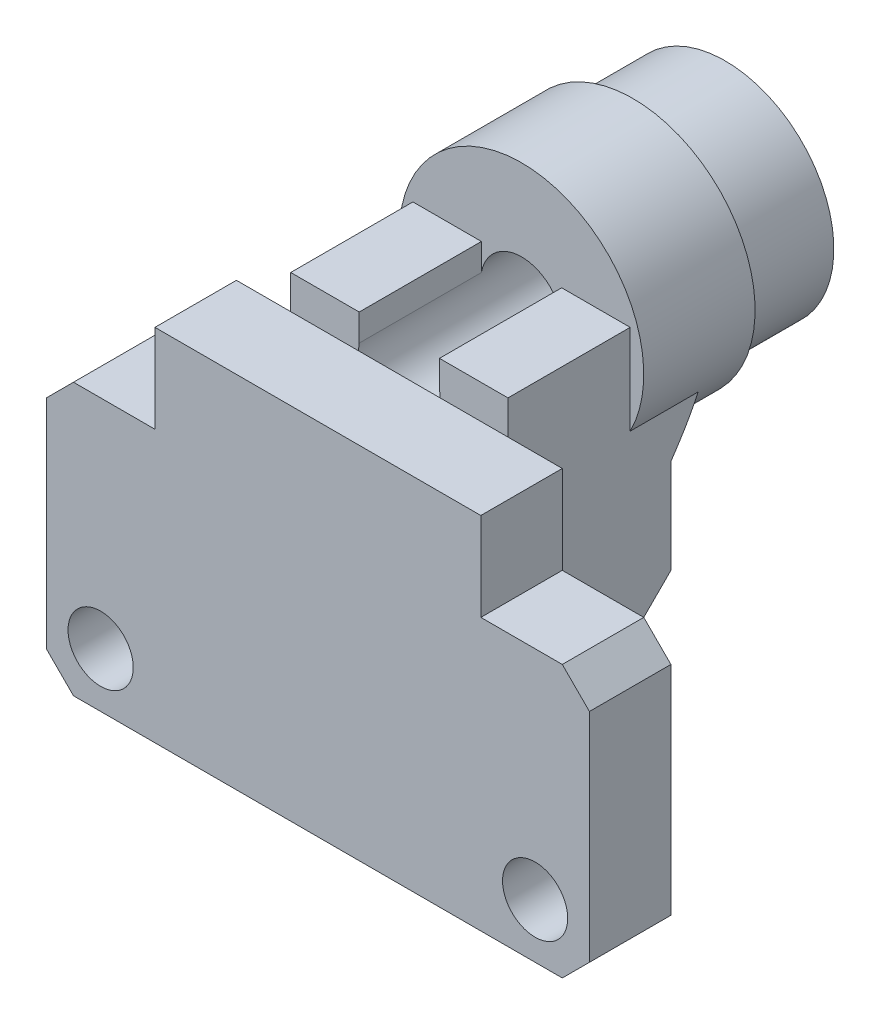
SolidWorks part; units mm, degrees
material "ABS"
ref_plane "Front Plane" through (0, 0, 0) normal (0, 0, 1) x (1, 0, 0)
ref_plane "Top Plane" through (0, 0, 0) normal (0, 1, 0) x (1, 0, 0)
ref_plane "Right Plane" through (0, 0, 0) normal (1, 0, 0) x (0, 0, -1)
sketch "Sketch1" plane through (0, 0, 0) normal (0, 0, 1) x (1, 0, 0)
  line L0 (0, 78.4471) -> (0, -76.9705) construction
  line L1 (-83.0616, 0) -> (77.155, 0) construction
  line L3 (-10, 5) -> (10, 5)
  line L4 (-10, 5) -> (-10, -5)
  line L5 (-10, -5) -> (10, -5)
  line L6 (10, 5) -> (10, -5)
  dimension "D1" = 20
  dimension "D2" = 10
extrude "Boss-Extrude1" add sketch "Sketch1" along normal blind 3
sketch "Sketch2" plane through (0, 0, 0) normal (0, 0, -1) x (-1, 0, 0)
  line L0 (0, -15.2672) -> (0, 42.8631) construction
  line L1 (4, 0) -> (-4, 0)
  line L2 (4, 0) -> (4, 9.5)
  line L3 (4, 9.5) -> (-4, 9.5)
  line L4 (-4, 0) -> (-4, 9.5)
  line L5 (-10, 5) -> (10, 5) construction
  dimension "D1" = 8
  dimension "D2" = 4.5
extrude "Boss-Extrude2" add sketch "Sketch2" along normal blind 6
sketch "Sketch3" plane through (0, 0, -6) normal (0, 0, -1) x (-1, 0, 0)
  line L0 (-4, 0) -> (4, 0) construction
  circle A0 centre (0, 8.25) radius 4.5
  dimension "D1" = 9
  dimension "D2" = 8.25
extrude "Boss-Extrude3" add sketch "Sketch3" along normal blind 6 and the other way blind 1.5
ref_plane "Plane1" through (0, 0, 3) normal (0, 0, 1) x (1, 0, 0)
hole_wizard "Ø3.0 (3) Diameter Hole1" positions "Sketch4" profile "Sketch5" hole size "Ø3.0" standard "ISO" end condition through all
sketch "Sketch4" plane through (0, 0, -12) normal (0, 0, -1) x (-1, 0, 0)
  circle A0 centre (0, 8.25) radius 4.5 construction
  point P0 (0, 8.25)
sketch "Sketch5" plane through (0, 8.25, -12) normal (1, 0, 0) x (0, 1, 0)
  line L0 (0, 0) -> (0, 15)
  line L1 (0, 15) -> (1.5, 15)
  line L2 (1.5, 15) -> (1.5, 0)
  line L5 (1.5, 0) -> (0, 0)
  line L11 (0, -6.35) -> (0, 107.95) construction
  dimension "Thru Hole Dia." = 3
  dimension "Thru Hole Depth" = 15
sketch "Sketch6" plane through (0, 0, 0) normal (0, 0, 1) x (1, 0, 0)
  line L0 (-1.4774, 8.5094) -> (-1.4774, 9.5)
  line L1 (-4, 9.5) -> (-0.8292, 9.5) construction
  line L2 (-1.4774, 9.5) -> (1.4774, 9.5)
  line L3 (1.4774, 9.5) -> (1.4774, 8.5094)
  line L4 (1.4774, 8.5094) -> (-1.4774, 8.5094)
  circle A0 centre (0, 8.25) radius 1.5 construction
extrude "Cut-Extrude1" cut sketch "Sketch6" against normal blind 4.5
chamfer "Chamfer1" distance 1 angle 45 4 edges at (-10, 5, 1.5) (10, 5, 1.5) (10, -5, 1.5) (-10, -5, 1.5)
sketch "Sketch7" plane through (0, 0, -6) normal (0, 0, -1) x (-1, 0, 0)
  line L0 (-4.5, 8.25) -> (-5.6094, 8.25)
  line L1 (-5.6094, 8.25) -> (-5.6094, 15.8966)
  line L2 (-5.6094, 15.8966) -> (5.7054, 15.8966)
  line L3 (5.7054, 15.8966) -> (5.7054, 8.25)
  line L4 (5.7054, 8.25) -> (4.5, 8.25)
  arc A0 (4.5, 8.25) -> (-4.5, 8.25) centre (0, 8.25) ccw
chamfer "Chamfer2" distance 1 angle 45 4 edges at (0, 0, -6) (0, 0, 0) (4, 2.5, 0) (-4, 2.5, 0)
chamfer "Chamfer3" distance 1 angle 45 1 edges at (0, 3.75, -6)
sketch "Sketch8" plane through (0, 0, -12) normal (0, 0, -1) x (-1, 0, 0)
  circle A0 centre (0, 8.25) radius 4
  circle A1 centre (0, 8.25) radius 4.5
  dimension "D1" = 8
extrude "Cut-Extrude3" cut sketch "Sketch8" against normal blind 3.4
chamfer "Chamfer4" distance 2 angle 45 1 edges at (0, 5, 0)
chamfer "Chamfer5" distance 2 angle 45 2 edges at (4, 5, 0.5) (-4, 5, 0.5)
hole_wizard "M2 Clearance Hole1" positions "Sketch9" profile "Sketch10" hole size "M2" standard "ISO" end condition through all
sketch "Sketch9" plane through (0, 0, 0) normal (0, 0, -1) x (-1, 0, 0)
  line L0 (0, 17.4642) -> (0, -12.0288) construction
  line L2 (-18.4305, -3) -> (19.5599, -3) construction
  line L4 (10, 4) -> (10, -4) construction
  line L5 (9, -5) -> (-9, -5) construction
  point P0 (8, -3)
  point P2 (-8, -3)
  dimension "D1" = 2
  dimension "D2" = 2
sketch "Sketch10" plane through (-8, -3, 0) normal (1, 0, 0) x (0, 1, 0)
  line L0 (0, 0) -> (0, 3)
  line L1 (0, 3) -> (1.2, 3)
  line L2 (1.2, 3) -> (1.2, 0)
  line L5 (1.2, 0) -> (0, 0)
  line L11 (0, -6.35) -> (0, 107.95) construction
  dimension "Thru Hole Dia." = 2.4
  dimension "Thru Hole Depth" = 3
ref_axis "Axis1" through (0, 8.25, -8.6) along (0, 0, -1)
hole_wizard "M1.6 Tapped Hole1" positions "Sketch11" profile "Sketch12" tap size "M1.6" standard "ISO"
sketch "Sketch11" plane through (0, 0, -12) normal (0, 0, -1) x (-1, 0, 0)
  line L0 (-5.1174, 8.25) -> (5.7056, 8.25) construction
  line L1 (0, 14.0942) -> (0, -5.7534) construction
  point P0 (2.75, 8.25)
  point P2 (-2.75, 8.25)
  dimension "D1" = 5.5
cosmetic thread "Hole Thread1" parameters "D1"=3.2, "D2"=1.6
cosmetic thread "Hole Thread2" parameters "D1"=3.2, "D2"=1.6
sketch "Sketch12" plane through (-2.75, 8.25, -12) normal (1, 0, 0) x (0, 1, 0)
  line L0 (0, 0) -> (0, 5.3755)
  line L1 (0, 5.3755) -> (0.625, 5)
  line L2 (0.625, 5) -> (0.625, 0)
  line L5 (0.625, 0) -> (0, 0)
  line L10 (0, 5.3755) -> (-0.625, 5) construction
  line L11 (0, -6.35) -> (0, 107.95) construction
  dimension "Tap Drill Dia." = 1.25
  dimension "Tap Drill Depth" = 5
  dimension "Drill Angle" = 118
sketch "Sketch13" plane through (0, 0, 3) normal (0, 0, 1) x (1, 0, 0)
  line L0 (-6, 8.25) -> (6, 8.25)
  line L3 (6, 8.25) -> (6, 5)
  line L5 (6, 5) -> (-6, 5)
  line L7 (-6, 5) -> (-6, 8.25)
  point P0 (0, 0)
extrude "Boss-Extrude5" add sketch "Sketch13" against normal up to surface (3 mm away) up to face at (-2.4018, 8.2826, 0)
